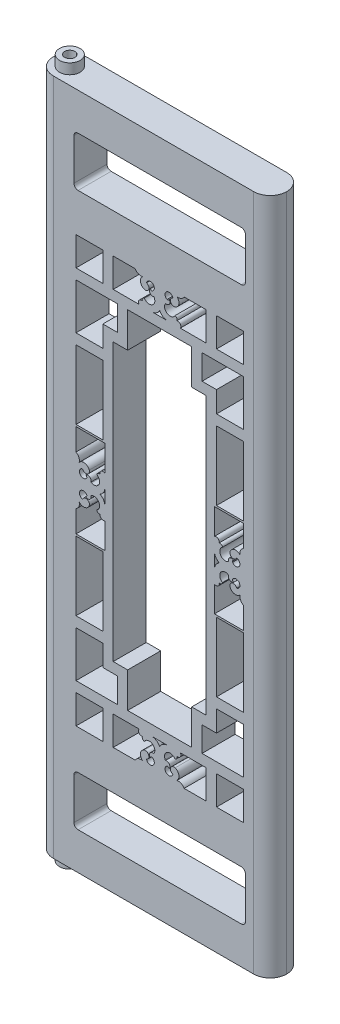
SolidWorks part; units mm, degrees
material "松木"
ref_plane "前视基准面" through (0, 0, 0) normal (0, 0, 1) x (1, 0, 0)
ref_plane "上视基准面" through (0, 0, 0) normal (0, 1, 0) x (1, 0, 0)
ref_plane "右视基准面" through (0, 0, 0) normal (1, 0, 0) x (0, 0, -1)
sketch "Sketch1" plane through (0, 0, 0) normal (0, 0, 1) x (1, 0, 0)
  line L0 (0, 0) -> (0, 1640)
  line L1 (0, 1640) -> (595, 1640)
  line L2 (595, 1640) -> (595, 0)
  line L3 (595, 0) -> (0, 0)
  dimension "D1" = 1640
  dimension "D2" = 595
extrude "Boss-Extrude1" add sketch "Sketch1" along normal blind 180
sketch "Sketch2" plane through (0, 0, 0) normal (0, 0, -1) x (-1, 0, 0)
  line L0 (-525, 1570) -> (-525, 70)
  line L1 (-525, 70) -> (-70, 70)
  line L2 (-70, 70) -> (-70, 1570)
  line L3 (-70, 1570) -> (-525, 1570)
  line L4 (-595, 0) -> (-595, 1640) construction
  line L5 (-595, 1640) -> (0, 1640) construction
  line L6 (-70, 1410) -> (-525, 1410)
  line L7 (-525, 230) -> (-70, 230)
  line L8 (-70, 1360) -> (-525, 1360)
  line L9 (-70, 280) -> (-525, 280)
  line L10 (-500, 1335) -> (-500, 305)
  line L11 (-500, 305) -> (-95, 305)
  line L12 (-95, 305) -> (-95, 1335)
  line L13 (-95, 1335) -> (-500, 1335)
  line L14 (-95, 1265) -> (-500, 1265)
  line L15 (-95, 1240) -> (-500, 1240)
  line L16 (-95, 375) -> (-500, 375)
  line L17 (-95, 400) -> (-500, 400)
  line L18 (-160, 1335) -> (-160, 1265)
  line L19 (-435, 1335) -> (-435, 1265)
  line L20 (-410, 1335) -> (-410, 1265)
  line L21 (-185, 1335) -> (-185, 1265)
  line L22 (-435, 375) -> (-435, 305)
  line L23 (-410, 375) -> (-410, 305)
  line L24 (-160, 375) -> (-160, 305)
  line L25 (-185, 375) -> (-185, 305)
  line L26 (-195, 400) -> (-195, 460)
  line L27 (-195, 460) -> (-160, 460)
  line L28 (-160, 460) -> (-160, 1180)
  line L29 (-160, 1180) -> (-195, 1180)
  line L30 (-195, 1180) -> (-195, 1240)
  line L31 (-400, 1240) -> (-400, 1180)
  line L32 (-400, 1180) -> (-435, 1180)
  line L33 (-435, 1180) -> (-435, 460)
  line L34 (-435, 460) -> (-400, 460)
  line L35 (-400, 460) -> (-400, 400)
  line L36 (-220, 1240) -> (-220, 1155)
  line L37 (-220, 1155) -> (-185, 1155)
  line L38 (-185, 1155) -> (-185, 485)
  line L39 (-185, 485) -> (-220, 485)
  line L40 (-220, 485) -> (-220, 400)
  line L41 (-375, 1240) -> (-375, 1155)
  line L42 (-375, 1155) -> (-410, 1155)
  line L43 (-410, 1155) -> (-410, 485)
  line L44 (-410, 485) -> (-375, 485)
  line L45 (-375, 485) -> (-375, 400)
  line L46 (-435, 1129) -> (-500, 1129)
  line L47 (-435, 1104) -> (-500, 1104)
  line L48 (-160, 1129) -> (-95, 1129)
  line L49 (-160, 1104) -> (-95, 1104)
  line L50 (-435, 511) -> (-500, 511)
  line L51 (-435, 536) -> (-500, 536)
  line L52 (-160, 511) -> (-95, 511)
  line L53 (-160, 536) -> (-95, 536)
  line L54 (-435, 937) -> (-500, 937)
  line L55 (-435, 919.4131) -> (-500, 919.4131)
  line L56 (-435, 703) -> (-500, 703)
  line L57 (-435, 728) -> (-500, 728)
  line L58 (-160, 919.4131) -> (-95, 919.4131)
  line L59 (-160, 937) -> (-95, 937)
  line L60 (-160, 703) -> (-95, 703)
  line L61 (-160, 728) -> (-95, 728)
  line L62 (-495, 210) -> (-100, 210)
  line L63 (-90, 200) -> (-90, 100)
  line L64 (-100, 90) -> (-495, 90)
  line L65 (-505, 100) -> (-505, 200)
  line L67 (-495, 1550) -> (-100, 1550)
  line L68 (-505, 1540) -> (-505, 1440)
  line L69 (-495, 1430) -> (-100, 1430)
  line L70 (-90, 1540) -> (-90, 1440)
  arc A0 (-495, 210) -> (-505, 200) centre (-495, 200) ccw
  arc A1 (-90, 200) -> (-100, 210) centre (-100, 200) ccw
  arc A2 (-505, 100) -> (-495, 90) centre (-495, 100) ccw
  arc A3 (-100, 90) -> (-90, 100) centre (-100, 100) ccw
  arc A4 (-495, 1550) -> (-505, 1540) centre (-495, 1540) ccw
  arc A5 (-90, 1540) -> (-100, 1550) centre (-100, 1540) ccw
  arc A6 (-505, 1440) -> (-495, 1430) centre (-495, 1440) ccw
  arc A7 (-100, 1430) -> (-90, 1440) centre (-100, 1440) ccw
  point P62 (-177.5, 1180)
  point P63 (-220, 442.5)
  point P64 (-177.5, 460)
  point P71 (-392.5, 485)
  dimension "D53" = 20
  dimension "D56" = 20
  dimension "D57" = 20
  dimension "D58" = 20
  dimension "D47" = 30
  dimension "D63" = 20
  dimension "D64" = 20
  dimension "D65" = 20
  dimension "D66" = 20
  dimension "D1" = 70
  dimension "D2" = 70
  dimension "D3" = 1500
  dimension "D4" = 455
  dimension "D5" = 160
  dimension "D6" = 160
  dimension "D7" = 50
  dimension "D8" = 50
  dimension "D9" = 25
  dimension "D10" = 25
  dimension "D11" = 25
  dimension "D12" = 25
  dimension "D13" = 70
  dimension "D14" = 25
  dimension "D15" = 25
  dimension "D16" = 70
  dimension "D17" = 65
  dimension "D18" = 65
  dimension "D19" = 25
  dimension "D20" = 25
  dimension "D21" = 100
  dimension "D22" = 100
  dimension "D23" = 60
  dimension "D24" = 60
  dimension "D25" = 35
  dimension "D26" = 35
  dimension "D27" = 100
  dimension "D28" = 35
  dimension "D29" = 60
  dimension "D30" = 60
  dimension "D31" = 25
  dimension "D32" = 25
  dimension "D33" = 25
  dimension "D34" = 25
  dimension "D35" = 25
  dimension "D36" = 25
  dimension "D37" = 25
  dimension "D38" = 25
  dimension "D39" = 111
  dimension "D40" = 25
  dimension "D41" = 111
  dimension "D42" = 25
  dimension "D43" = 167
  dimension "D44" = 17.5869
  dimension "D45" = 25
  dimension "D46" = 167
  dimension "D48" = 30
  dimension "D49" = 20
  dimension "D50" = 30
  dimension "D51" = 10
  dimension "D52" = 10
  dimension "D54" = 10
  dimension "D55" = 10
  dimension "D59" = 20
  dimension "D60" = 20
  dimension "D61" = 20
  dimension "D62" = 20
  dimension "D67" = 30
  dimension "D68" = 30
  dimension "D69" = 30
  dimension "D70" = 30
  dimension "D71" = 30
  dimension "D72" = 30
  dimension "D73" = 30
  dimension "D74" = 30
sketch "草图1" plane through (0, 0, 0) normal (0, 0, -1) x (-1, 0, 0)
  line L0 (-500, 305) -> (-95, 305) construction
  line L1 (-95, 375) -> (-500, 375) construction
  line L2 (-410, 375) -> (-410, 305) construction
  line L3 (-185, 375) -> (-185, 305) construction
  line L6 (-347.4491, 375) -> (-315.5, 375)
  line L7 (-279.5, 375) -> (-247.5509, 375)
  line L8 (-356.6733, 305) -> (-238.3267, 305)
  line L9 (-347.4491, 375) -> (-410, 375)
  line L10 (-410, 375) -> (-410, 305)
  line L11 (-410, 305) -> (-356.6733, 305)
  line L12 (-315.5, 375) -> (-279.5, 375)
  line L13 (-238.3267, 305) -> (-185, 305)
  line L14 (-185, 305) -> (-185, 375)
  line L15 (-185, 375) -> (-247.5509, 375)
  line L16 (-500, 707.5) -> (-430, 707.5)
  line L18 (-430, 802) -> (-430, 838)
  line L19 (-430, 707.5) -> (-430, 770.0509)
  line L20 (-430, 932.5) -> (-500, 932.5)
  line L22 (-500, 760.8267) -> (-500, 707.5)
  line L24 (-430, 869.9491) -> (-430, 932.5)
  line L25 (-500, 932.5) -> (-500, 879.1733)
  line L26 (-500, 879.1733) -> (-500, 1640) construction
  line L27 (-595, 707.5) -> (0, 707.5) construction
  line L28 (-595, 0) -> (-595, 1640) construction
  line L29 (0, 1640) -> (0, 0) construction
  line L30 (-500, 0) -> (-500, 760.8267) construction
  line L31 (0, 0) -> (-595, 0) construction
  line L32 (-595, 1640) -> (0, 1640) construction
  arc A0 (-297.5, 362.9626) -> (-315.5, 375) centre (-316.8257, 353.5409) ccw
  arc A1 (-279.5, 375) -> (-297.5, 362.9626) centre (-278.1743, 353.5409) ccw
  arc A2 (-311.5772, 341.0539) -> (-334.4772, 355.321) centre (-322.7578, 348.6199) ccw
  arc A4 (-260.5228, 355.321) -> (-283.4228, 341.0539) centre (-272.2422, 348.6199) ccw
  arc A5 (-347.4491, 375) -> (-339.4787, 363.4423) centre (-341.29, 370.7203) ccw
  arc A6 (-255.5213, 363.4423) -> (-247.5509, 375) centre (-253.71, 370.7203) ccw
  arc A7 (-339.4787, 363.4423) -> (-334.4772, 355.321) centre (-333.2172, 361.6977) ccw
  arc A8 (-260.5228, 355.321) -> (-255.5213, 363.4423) centre (-261.7828, 361.6977) ccw
  arc A9 (-297.5, 336.0027) -> (-311.5772, 341.0539) centre (-304.7324, 337.9882) ccw
  arc A10 (-283.4228, 341.0539) -> (-297.5, 336.0027) centre (-290.2676, 337.9882) ccw
  arc A11 (-311.5772, 341.0539) -> (-320.3587, 328.3114) centre (-314.2948, 333.5296) ccw
  arc A12 (-274.6413, 328.3114) -> (-283.4228, 341.0539) centre (-280.7052, 333.5296) ccw
  arc A13 (-315.214, 331.0064) -> (-320.3587, 328.3114) centre (-316.5099, 327.2221) ccw
  arc A14 (-274.6413, 328.3114) -> (-279.786, 331.0064) centre (-278.4901, 327.2221) ccw
  arc A16 (-279.786, 331.0064) -> (-265.6848, 320.9352) centre (-275, 322.8) ccw
  arc A17 (-329.3152, 320.9352) -> (-334.7689, 337.0364) centre (-332, 329) ccw
  arc A18 (-260.2311, 337.0364) -> (-265.6848, 320.9352) centre (-263, 329) ccw
  arc A19 (-329.3152, 320.9352) -> (-315.214, 331.0064) centre (-320, 322.8) ccw
  arc A20 (-463.9461, 834.0772) -> (-476.6886, 842.8587) centre (-471.4704, 836.7948) ccw
  arc A21 (-334.7689, 337.0364) -> (-338.5296, 312.5413) centre (-330.2084, 323.8) ccw
  arc A23 (-338.5296, 312.5413) -> (-356.6733, 305) centre (-343, 297.7) ccw
  arc A24 (-238.3267, 305) -> (-256.4704, 312.5413) centre (-252, 297.7) ccw
  arc A25 (-256.4704, 312.5413) -> (-260.2311, 337.0364) centre (-264.7916, 323.8) ccw
  arc A26 (-473.9936, 837.714) -> (-476.6886, 842.8587) centre (-477.7779, 839.0099) ccw
  arc A27 (-463.9461, 805.9228) -> (-462.5046, 806.773) centre (-467.0118, 812.7676) ccw
  arc A28 (-484.0648, 851.8152) -> (-467.9636, 857.2689) centre (-476, 854.5) ccw
  arc A29 (-430, 869.9491) -> (-441.5577, 861.9787) centre (-434.2797, 863.79) ccw
  arc A30 (-467.9636, 857.2689) -> (-492.4587, 861.0296) centre (-481.2, 852.7084) ccw
  arc A31 (-442.0374, 820) -> (-430, 838) centre (-451.4591, 839.3257) ccw
  arc A32 (-441.5577, 861.9787) -> (-449.679, 856.9772) centre (-443.3023, 855.7172) ccw
  arc A33 (-467.9636, 782.7311) -> (-484.0648, 788.1848) centre (-476, 785.5) ccw
  arc A34 (-476.6886, 797.1413) -> (-463.9461, 805.9228) centre (-471.4704, 803.2052) ccw
  arc A35 (-476.6886, 797.1413) -> (-473.9936, 802.286) centre (-477.7779, 800.9901) ccw
  arc A36 (-441.5577, 778.0213) -> (-430, 770.0509) centre (-434.2797, 776.21) ccw
  arc A37 (-492.4587, 778.9704) -> (-467.9636, 782.7311) centre (-481.2, 787.2916) ccw
  arc A38 (-449.679, 783.0228) -> (-463.9461, 805.9228) centre (-456.3801, 794.7422) ccw
  arc A39 (-484.0648, 851.8152) -> (-473.9936, 837.714) centre (-482.2, 842.5) ccw
  arc A40 (-500, 760.8267) -> (-492.4587, 778.9704) centre (-507.3, 774.5) ccw
  arc A41 (-449.679, 783.0228) -> (-441.5577, 778.0213) centre (-443.3023, 784.2828) ccw
  arc A42 (-473.9936, 802.286) -> (-484.0648, 788.1848) centre (-482.2, 797.5) ccw
  arc A43 (-463.9461, 834.0772) -> (-449.679, 856.9772) centre (-456.3801, 845.2578) ccw
  arc A44 (-492.4587, 861.0296) -> (-500, 879.1733) centre (-507.3, 865.5) ccw
  arc A46 (-430, 802) -> (-442.0374, 820) centre (-451.4591, 800.6743) ccw
  arc A48 (-462.5046, 833.227) -> (-463.9461, 834.0772) centre (-467.0118, 827.2324) ccw
  dimension "D5" = 37.0118
  dimension "D6" = 105.2676
  dimension "D11" = 27
  dimension "D12" = 27
  dimension "D13" = 15
  dimension "D10" = 15
  dimension "D15" = 13
  dimension "D16" = 13
  dimension "D2" = 15
  dimension "D3" = 15
  dimension "D8" = 16
  dimension "D9" = 16
  dimension "D18" = 8
  dimension "D19" = 8
  dimension "D24" = 9.5
  dimension "D25" = 19
  dimension "D30" = 17
  dimension "D31" = 17
  dimension "D36" = 28
  dimension "D37" = 95
  dimension "D40" = 31
  dimension "D41" = 31
  dimension "D4" = 37.0118
  dimension "D7" = 105.2676
  dimension "D14" = 95.7052
  dimension "D17" = 95.7052
  dimension "D20" = 47.7779
  dimension "D21" = 47.7779
  dimension "D22" = 93.4901
  dimension "D23" = 93.4901
  dimension "D26" = 90
  dimension "D27" = 90
  dimension "D28" = 52.2
  dimension "D29" = 52.2
  dimension "D32" = 24
  dimension "D33" = 24
  dimension "D34" = 78
  dimension "D35" = 78
  dimension "D38" = 18.8
  dimension "D39" = 707.5
  dimension "D42" = 7.3
  dimension "D43" = 7.3
  dimension "D44" = 67
  dimension "D45" = 67
sketch "草图5" plane through (0, 0, 0) normal (0, 0, -1) x (-1, 0, 0)
sketch "草图6" plane through (0, 0, 180) normal (0, 0, 1) x (1, 0, 0)
  line L0 (0, 1640) -> (0, 0)
  line L1 (0, 0) -> (595, 0)
  line L2 (595, 0) -> (595, 1640)
  line L3 (595, 1640) -> (0, 1640)
extrude "切除-拉伸2" cut sketch "草图6" against normal blind 100
extrude "切除-拉伸3" cut sketch "草图1" against normal blind 100 contours A23 A21 A17 A19 A13 A11 A9 A2 A7 A5 L9 L10 L11 | A25 A24 L13 L14 L15 A6 A8 A4 A10 A12 A14 A16 A18 | A1 L12 A0 region at (368.1315, 340.5137, 0) region at (297.5, 371.6597, 0) region at (226.8685, 340.5137, 0)
extrude "切除-拉伸5" cut sketch "Sketch2" against normal through all contours L64 A3 L63 A1 L62 A0 L65 A2 | L22 L16 L10 L11 | L16 L24 L11 L12 | L33 L50 L10 L17 L35 L34 | L52 L28 L27 L26 L17 L12 | L33 L56 L10 L51 | L60 L28 L53 L12 | L44 L45 L17 L40 L39 L38 L37 L36 L15 L41 L42 L43 | L54 L33 L47 L10 | L28 L59 L12 L49 | L28 L48 L12 L15 L30 L29 | L13 L18 L14 L12 | L19 L13 L10 L14 | L46 L33 L32 L31 L15 L10 | L69 A7 L70 A5 L67 A4 L68 A6 region at (467.5, 1300, 0) region at (456.2279, 1190.2488, 0) region at (467.5, 1020.5, 0) region at (297.5, 820, 0) region at (127.5, 1300, 0) region at (138.7721, 1190.2488, 0) region at (467.5, 619.5, 0) region at (127.5, 1020.5, 0) region at (456.2279, 449.7512, 0) region at (138.7721, 449.7512, 0) region at (467.5, 340, 0) region at (127.5, 619.5, 0) region at (127.5, 340, 0) region at (297.5, 150, 0) region at (297.5, 1490, 0)
ref_plane "基准面1" through (0, 820, 0) normal (0, 1, 0) x (1, 0, 0)
mirror "镜向1" about plane through (0, 820, 0) normal (0, 1, 0) of "切除-拉伸3"
extrude "切除-拉伸8" cut sketch "草图1<5>" against normal through all contours A48 A43 A32 A29 L24 L20 L25 A44 A30 A28 A39 A26 A20 | A35 A42 A33 A37 A40 L22 L16 L19 A36 A41 A38 A27 A34 | A31 L18 A46 region at (464.4863, 749.3685, 0) region at (464.4863, 890.6315, 0)
sketch "草图1<5>" plane through (0, 0, 0) normal (0, 0, -1) x (-1, 0, 0) same geometry as "草图1"
ref_plane "基准面3" through (297.5, 0, 0) normal (-1, 0, 0) x (0, 0, 1)
mirror "镜向3" about plane through (297.5, 0, 0) normal (-1, 0, 0) of "切除-拉伸8"
fillet "圆角1" radius 40 2 edges at (0, 820, 0) (0, 820, 80)
sketch "草图7" plane through (0, 1640, 0) normal (0, 1, 0) x (1, 0, 0)
  circle A0 centre (40, -40) radius 25
  dimension "D1" = 50
  dimension "D2" = 40
extrude "凸台-拉伸1" add sketch "草图7" along normal blind 25
ref_plane "基准面4" through (0, 820, 0) normal (0, 1, 0) x (1, 0, 0)
mirror "镜向4" about plane through (0, 820, 0) normal (0, 1, 0) of "凸台-拉伸1"
sketch "草图8" plane through (0, 1665, 0) normal (0, 1, 0) x (1, 0, 0)
  circle A0 centre (40, -40) radius 12.5
  dimension "D1" = 25
extrude "切除-拉伸9" cut sketch "草图8" against normal through all
sketch "草图9" plane through (595, 0, 0) normal (1, 0, 0) x (0, 0, -1)
  line L1 (-80, 1640) -> (0, 1640)
  line L2 (-80, 1640) -> (-80, 0)
  line L3 (-80, 0) -> (0, 0)
  line L4 (0, 1640) -> (0, 0)
extrude "切除-拉伸10" cut sketch "草图9" against normal blind 30
fillet "圆角2" radius 40 2 edges at (565, 820, 0) (565, 820, 80)
